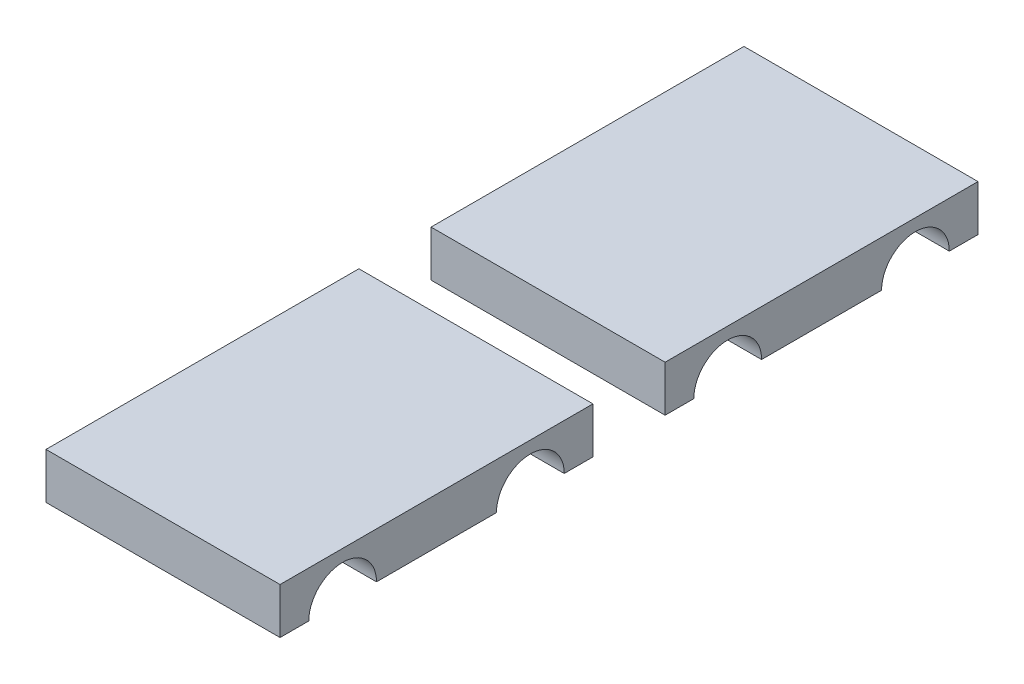
SolidWorks part; units mm, degrees
note: The reader was unsure of these and kept them because the rebuilt part matched: shared geometry of "Sketch9<3>", "Sketch9<4>".
ref_plane "Front Plane" through (0, 0, 0) normal (0, 0, 1) x (1, 0, 0)
ref_plane "Top Plane" through (0, 0, 0) normal (0, 1, 0) x (1, 0, 0)
ref_plane "Right Plane" through (0, 0, 0) normal (1, 0, 0) x (0, 0, -1)
sketch "Sketch6" plane through (0, 0, 0) normal (0, 1, 0) x (1, 0, 0)
  line L0 (0, 0) -> (0, 5)
  line L1 (0, 5) -> (19, 5)
  line L2 (19, 5) -> (19, 2.75)
  line L6 (19, 2.75) -> (16, 2.75)
  line L7 (16, 2.75) -> (15, 2.25)
  line L8 (15, 2.25) -> (15, 2.75)
  line L9 (15, 2.75) -> (9, 2.75)
  line L10 (9, 2.75) -> (8, 2.25)
  line L11 (8, 2.25) -> (8, 2.75)
  line L12 (8, 2.75) -> (0, 2.75)
  line L18 (0, 0) -> (15, 0)
  dimension "D1" = 0.5
  dimension "D2" = 19
  dimension "D3" = 3
  dimension "D4" = 5
  dimension "D5" = 2.25
  dimension "D6" = 2.25
  dimension "D7" = 2.25
  dimension "D10" = 1
  dimension "D11" = 1
  dimension "D12" = 6
  dimension "D13" = 8
  dimension "D20" = 15
revolve "Revolve1" add sketch "Sketch6" angle 180 about L18
sketch "Sketch9" plane through (0, 0, 0) normal (0, 0, 1) x (1, 0, 0)
  line L0 (0, 0) -> (0, 3.25)
  line L1 (0, 3.25) -> (0, 5)
  line L2 (0, 5) -> (19, 5)
  line L3 (19, 5) -> (19, 2.75)
  line L4 (19, 2.75) -> (19, 0)
  line L5 (19, 0) -> (0, 0)
  line L6 (0, 3.25) -> (19, 2.75)
  dimension "D1" = 3.25
extrude "Boss-Extrude1" add sketch "Sketch9" along normal blind 9.25 and the other way blind 9.25 contours L1 L6 L3 L2
extrude "Boss-Extrude2" add sketch "Sketch9<3>" along normal blind 5.75 from offset 3.5 contours L6 L0 L5 L4
sketch "Sketch9<3>" plane through (0, 0, 0) normal (0, 0, 1) x (1, 0, 0) same geometry as "Sketch9"
extrude "Boss-Extrude3" add sketch "Sketch9<4>" against normal blind 5.75 from offset 3.5 contours L6 L0 L5 L4 offset against normal yes
sketch "Sketch9<4>" plane through (0, 0, 0) normal (0, 0, 1) x (1, 0, 0) same geometry as "Sketch9"
sketch "Sketch13" plane through (0, 0, 0) normal (-1, 0, 0) x (0, 0, 1)
  line L0 (-2.75, 0) -> (-9.25, 0) construction
  line L1 (-2.75, 0) -> (2.75, 0)
  line L2 (-2.75, 0) -> (-2.75, 2.75)
  line L3 (-2.75, 2.75) -> (2.75, 2.75)
  line L4 (2.75, 0) -> (2.75, 2.75)
  point P6 (0, 0)
  dimension "D1" = 5.5
  dimension "D2" = 2.75
extrude "Cut-Extrude9" cut sketch "Sketch13" against normal blind 1.75
ref_plane "Plane3" through (0, 0, -7.62) normal (0, 0, 1) x (1, 0, 0)
mirror "Mirror4" about plane through (0, 0, -7.62) normal (0, 0, 1) of bodies 146
sketch "Sketch16" plane through (0, 5, 0) normal (0, 1, 0) x (1, 0, 0)
  line L0 (0, 24.49) -> (0, -9.25) construction
  line L1 (0, 20.32) -> (19, 20.32)
  line L2 (0, 20.32) -> (0, -5.08)
  line L3 (0, -5.08) -> (19, -5.08)
  line L4 (19, 20.32) -> (19, -5.08)
  line L5 (19, 24.49) -> (19, -9.25) construction
  dimension "D1" = 2.33
  dimension "D2" = 2.33
extrude "Cut-Extrude10" cut sketch "Sketch16" against normal through all
sketch "Sketch17" plane through (0, 5, 0) normal (0, 1, 0) x (1, 0, 0)
  line L1 (0, -5.08) -> (19, -5.08)
  line L2 (0, -5.08) -> (0, 20.32)
  line L3 (0, 20.32) -> (19, 20.32)
  line L4 (19, -5.08) -> (19, 20.32)
extrude "Cut-Extrude13" cut sketch "Sketch17" against normal blind 1.27
ref_plane "Plane5" through (0, 0, -23.25) normal (0, 0, -1) x (-1, 0, 0)
mirror "Mirror1" about plane through (0, 0, -23.25) normal (0, 0, -1) of bodies 157 122 138 137 141
